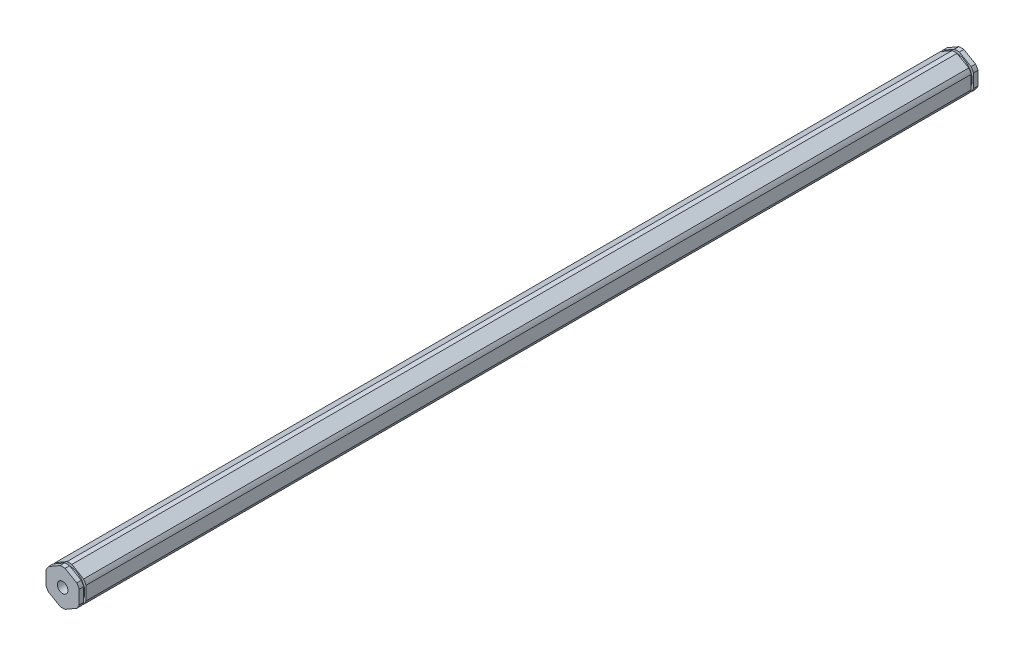
SolidWorks part; units mm, degrees
ref_plane "Front Plane" through (0, 0, 0) normal (0, 0, 1) x (1, 0, 0)
ref_plane "Top Plane" through (0, 0, 0) normal (0, 1, 0) x (1, 0, 0)
ref_plane "Right Plane" through (0, 0, 0) normal (1, 0, 0) x (0, 0, -1)
sketch "Sketch1" plane through (0, 0, 0) normal (0, 0, 1) x (1, 0, 0)
  line L1 (0, 7.3323) -> (-6.35, 3.6662)
  line L2 (-6.35, 3.6662) -> (-6.35, -3.6662)
  line L3 (-6.35, -3.6662) -> (0, -7.3323)
  line L4 (0, -7.3323) -> (6.35, -3.6662)
  line L5 (6.35, -3.6662) -> (6.35, 3.6662)
  line L6 (6.35, 3.6662) -> (0, 7.3323)
  circle A0 centre (0, 0) radius 6.35 construction
  circle A1 centre (0, 0) radius 6.858
  dimension "D1" = 12.7
  dimension "D2" = 13.716
extrude "Boss-Extrude1" add sketch "Sketch1" along normal mid plane 343.4715 contours L5 A1 L6 L1 L2 L3 L4 region at (0, 0, 0)
hole_wizard "#10-32 Tapped Hole1" positions "3DSketch1" profile "Sketch2" tap size "#10-32" standard "ANSI Inch"
sketch3d "3DSketch1"
  line L0 (0, 0, 171.7357) -> (0, 0, -171.7357) construction
  line L1 (0, 0, 171.7357) -> (0, 0, -171.7357) construction
  point P0 (0, 0, 171.7357)
  point P4 (0, 0, -171.7357)
sketch "Sketch2" plane through (0, 0, 171.7357) normal (1, 0, 0) x (0, -1, 0)
  line L0 (0, 0) -> (0, 17.5608)
  line L1 (0, 17.5608) -> (2.0193, 16.3474)
  line L2 (2.0193, 16.3474) -> (2.0193, 0)
  line L5 (2.0193, 0) -> (0, 0)
  line L10 (0, 17.5608) -> (-2.0193, 16.3474) construction
  line L11 (0, -6.35) -> (0, 107.95) construction
  dimension "Tap Drill Dia." = 4.0386
  dimension "Tap Drill Depth" = 16.3474
  dimension "Drill Angle" = 118
cosmetic thread "Hole Thread1" parameters "D1"=13.97, "D2"=4.826
cosmetic thread "Hole Thread2" parameters "D1"=13.97, "D2"=4.826
sketch "Sketch5" plane through (0, 0, 0) normal (1, 0, 0) x (0, 0, -1)
  line L0 (171.7357, 6.858) -> (-171.7357, 6.858) construction
  line L1 (-170.0212, 6.858) -> (-169.1322, 6.858)
  line L2 (-170.0212, 6.858) -> (-170.0212, 5.8547)
  line L3 (-170.0212, 5.8547) -> (-169.1322, 5.8547)
  line L4 (-169.1322, 6.858) -> (-169.1322, 5.8547)
  line L5 (-165.0472, 0) -> (-158.8423, 0) construction
  dimension "D1" = 5.8547
  dimension "D2" = 0.889
  dimension "D3" = 1.7145
revolve "Cut-Revolve1" cut sketch "Sketch5" angle 360 about L5
mirror "Mirror1" about plane through (0, 0, 0) normal (0, 0, 1) of "Cut-Revolve1"
